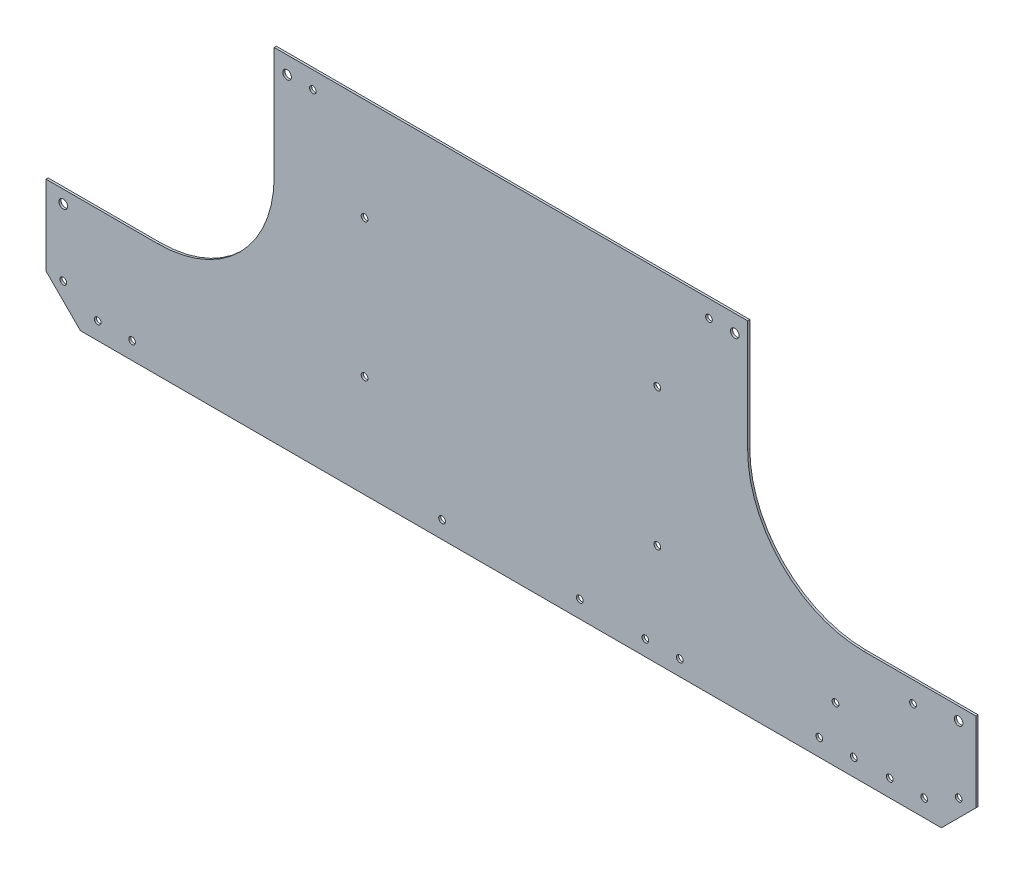
SolidWorks part; units mm, degrees
material "Perspex (TM) GS Acrylic Cast Sheet"
ref_plane "Front Plane" through (0, 0, 0) normal (0, 0, 1) x (1, 0, 0)
ref_plane "Top Plane" through (0, 0, 0) normal (0, 1, 0) x (1, 0, 0)
ref_plane "Right Plane" through (0, 0, 0) normal (1, 0, 0) x (0, 0, -1)
sketch "Sketch1" plane through (0, 0, 0) normal (0, 0, 1) x (1, 0, 0)
  line L1 (-457.2, -304.8) -> (457.2, -304.8)
  line L2 (-457.2, -304.8) -> (-457.2, 304.8)
  line L3 (-457.2, 304.8) -> (457.2, 304.8)
  line L4 (457.2, -304.8) -> (457.2, 304.8)
  line L5 (0, 304.8) -> (0, -304.8) construction
  line L6 (-457.2, 0) -> (457.2, 0) construction
  point P0 (0, 0)
  point P4 (-320.04, 0)
  point P5 (320.04, 0)
  point P6 (0, 213.36)
  point P7 (0, -213.36)
  dimension "Length" = 914.4
  dimension "Width" = 609.6
  dimension "Break" = 137.16
  dimension "D2" = 137.16
  dimension "D1" = 91.44
  dimension "D3" = 91.44
sketch "Sketch2" plane through (0, 0, 0) normal (1, 0, 0) x (0, 0, -1)
  line L0 (-0.7938, -304.8) -> (0.7938, -304.8)
  dimension "Thickness" = 1.5875
sketch "Sketch3" plane through (0, 0, 0) normal (0, 0, 1) x (1, 0, 0)
  line L0 (-457.2, -304.8) -> (-457.2, 304.8) construction
  line L1 (-457.2, -304.8) -> (457.2, -304.8) construction
  line L2 (457.2, -304.8) -> (457.2, 304.8) construction
  line L3 (-457.2, 304.8) -> (457.2, 304.8) construction
  line L4 (-457.2, -304.8) -> (-457.2, 304.8)
  line L5 (-457.2, -304.8) -> (457.2, -304.8)
  line L6 (457.2, -304.8) -> (457.2, 304.8)
  line L7 (-457.2, 304.8) -> (457.2, 304.8)
extrude "Boss-Extrude1" add sketch "Sketch3" along normal mid plane 1.5875
sketch "Sketch4" plane through (0, 0, 0.7937) normal (0, 0, 1) x (1, 0, 0)
  line L5 (-326.7349, -279.5815) -> (-352.1349, -254.1815)
  line L12 (308.2651, -279.5815) -> (333.6651, -254.1815)
  line L19 (-352.1349, -254.1815) -> (-352.1349, -29.709)
  line L20 (-349.5949, -27.169) -> (331.1251, -27.169)
  line L21 (-326.7349, -279.5815) -> (308.2651, -279.5815)
  line L22 (308.2651, -27.169) -> (308.2651, -687.569) construction
  line L23 (308.2651, -279.5815) -> (-326.7349, -279.5815) construction
  line L26 (333.6651, -254.1815) -> (333.6651, -29.709)
  arc A0 (333.6651, -29.709) -> (331.1251, -27.169) centre (331.1251, -29.709) ccw
  arc A1 (-349.5949, -27.169) -> (-352.1349, -29.709) centre (-349.5949, -29.709) ccw
  point P20 (333.6651, -27.169)
  point P23 (-352.1349, -27.169)
  dimension "D1" = 2.54
  dimension "D2" = 2.54
extrude "Cut-Extrude1" cut sketch "Sketch4" against normal blind 2.54 flip side to cut
sketch "Sketch7" plane through (0, 0, 0.7937) normal (0, 0, 1) x (1, 0, 0)
  line L6 (-269.5849, -173.219) -> (-352.1349, -173.219) construction
  line L18 (-352.1349, -712.969) -> (-352.1349, -52.569) construction
  line L24 (-352.1349, -173.219) -> (-352.1349, -27.169) construction
  line L25 (-206.0849, -109.719) -> (-206.0849, -27.169) construction
  line L26 (-352.1349, -27.169) -> (308.2651, -27.169) construction
  line L27 (-206.0849, -27.169) -> (-352.1349, -27.169) construction
  line L28 (-269.5849, -195.444) -> (-374.3599, -195.444)
  line L29 (-374.3599, -195.444) -> (-374.3599, -4.944)
  line L30 (-183.8599, -4.944) -> (-374.3599, -4.944)
  line L31 (-183.8599, -109.719) -> (-183.8599, -4.944)
  arc A5 (-206.0849, -109.719) -> (-269.5849, -173.219) centre (-269.5849, -109.719) cw construction
  arc A6 (-183.8599, -109.719) -> (-269.5849, -195.444) centre (-269.5849, -109.719) cw
  dimension "D1" = 22.225
extrude "Cut-Extrude2" cut sketch "Sketch7" against normal blind 2.54
sketch "Sketch8" plane through (0, 0, 0.7937) normal (0, 0, 1) x (1, 0, 0)
  line L18 (187.6151, -109.719) -> (187.6151, -27.169) construction
  line L19 (-352.1349, -27.169) -> (308.2651, -27.169) construction
  line L20 (187.6151, -27.169) -> (333.6651, -27.169) construction
  line L21 (251.1151, -173.219) -> (333.6651, -173.219) construction
  line L22 (333.6651, -27.169) -> (333.6651, -687.569) construction
  line L23 (333.6651, -173.219) -> (333.6651, -27.169) construction
  line L24 (251.1151, -195.444) -> (355.8901, -195.444)
  line L25 (355.8901, -195.444) -> (355.8901, -4.944)
  line L26 (165.3901, -4.944) -> (355.8901, -4.944)
  line L27 (165.3901, -109.719) -> (165.3901, -4.944)
  arc A4 (187.6151, -109.719) -> (251.1151, -173.219) centre (251.1151, -109.719) ccw construction
  arc A5 (165.3901, -109.719) -> (251.1151, -195.444) centre (251.1151, -109.719) ccw
  dimension "D1" = 22.225
extrude "Cut-Extrude3" cut sketch "Sketch8" against normal blind 2.54
sketch "Sketch9" plane through (0, 0, 0.7937) normal (0, 0, 1) x (1, 0, 0)
  point P0 (-339.4349, -254.1815)
  point P1 (-314.0349, -266.8815)
  point P3 (-288.6349, -266.8815)
  point P5 (-339.4349, -204.969)
  point P7 (89.9521, -268.1131)
  point P9 (115.3521, -268.1131)
  point P11 (218.2221, -266.8815)
  point P13 (243.6221, -266.8815)
  point P15 (270.1651, -266.8815)
  point P17 (295.5651, -266.8815)
  point P19 (320.9651, -254.1815)
  point P21 (320.9651, -204.969)
  point P23 (-155.2849, -39.869)
  point P25 (136.8151, -39.869)
hole_wizard "#10 (0.1935) Diameter Hole1" positions "Sketch10" profile "Sketch11" hole size "#10" standard "ANSI Inch" end condition through all
sketch "Sketch10" plane through (0, 0, 0.7937) normal (0, 0, 1) x (1, 0, 0)
  point P0 (-288.6349, -266.8815)
  point P3 (-314.0349, -266.8815)
  point P6 (-339.4349, -254.1815)
  point P9 (89.9521, -268.1131)
  point P12 (115.3521, -268.1131)
  point P15 (218.2221, -266.8815)
  point P18 (243.6221, -266.8815)
  point P21 (295.5651, -266.8815)
  point P24 (270.1651, -266.8815)
  point P27 (320.9651, -254.1815)
  point P31 (136.8151, -39.869)
  point P34 (-155.2849, -39.869)
  point P37 (-60.0349, -266.8815)
  point P40 (41.5651, -266.8815)
sketch "Sketch11" plane through (-288.6349, -266.8815, 0.7937) normal (1, 0, 0) x (0, -1, 0)
  line L0 (0, 0) -> (0, 1.5875)
  line L1 (0, 1.5875) -> (2.4574, 1.5875)
  line L2 (2.4574, 1.5875) -> (2.4574, 0)
  line L5 (2.4574, 0) -> (0, 0)
  line L11 (0, -6.35) -> (0, 107.95) construction
  dimension "Thru Hole Dia." = 4.9149
  dimension "Thru Hole Depth" = 1.5875
hole_wizard "1/4 (0.25) Diameter Hole1" positions "Sketch12" profile "Sketch13" hole size "1/4" standard "ANSI Inch" end condition through all
sketch "Sketch12" plane through (0, 0, 0.7937) normal (0, 0, 1) x (1, 0, 0)
  point P0 (-339.4349, -204.969)
  point P3 (320.9651, -204.969)
  point P7 (155.8651, -39.869)
  point P10 (-174.3349, -39.869)
sketch "Sketch13" plane through (-339.4349, -204.969, 0.7937) normal (1, 0, 0) x (0, -1, 0)
  line L0 (0, 0) -> (0, 1.5875)
  line L1 (0, 1.5875) -> (3.175, 1.5875)
  line L2 (3.175, 1.5875) -> (3.175, 0)
  line L5 (3.175, 0) -> (0, 0)
  line L11 (0, -6.35) -> (0, 107.95) construction
  dimension "Thru Hole Dia." = 6.35
  dimension "Thru Hole Depth" = 1.5875
hole_wizard "#10 Clearance Hole1" positions "Sketch14" profile "Sketch15" hole size "#10" standard "ANSI Inch" end condition through all
sketch "Sketch14" plane through (0, 0, 0.7937) normal (0, 0, 1) x (1, 0, 0)
  point P0 (-117.1849, -204.1753)
  point P3 (-117.1849, -102.5753)
  point P6 (98.7151, -102.5753)
  point P9 (98.7151, -204.1753)
  point P13 (230.1601, -238.7828)
  point P16 (287.3101, -210.8428)
sketch "Sketch15" plane through (-117.1849, -204.1753, 0.7937) normal (1, 0, 0) x (0, -1, 0)
  line L0 (0, 0) -> (0, 1.5875)
  line L1 (0, 1.5875) -> (2.4892, 1.5875)
  line L2 (2.4892, 1.5875) -> (2.4892, 0)
  line L5 (2.4892, 0) -> (0, 0)
  line L11 (0, -6.35) -> (0, 107.95) construction
  dimension "Thru Hole Dia." = 4.9784
  dimension "Thru Hole Depth" = 1.5875
equation "\"D1@Boss-Extrude1\"=\"thickness@sketch2\""
equation "\"Break@Sketch1\" = \"Length@Sketch1\" * 0.15"
equation "\"D2@Sketch1\" = \"Break@Sketch1\""
equation "\"D1@Sketch1\"=\"Width@Sketch1\"*0.15"
equation "\"D3@Sketch1\"=\"D1@Sketch1\""
